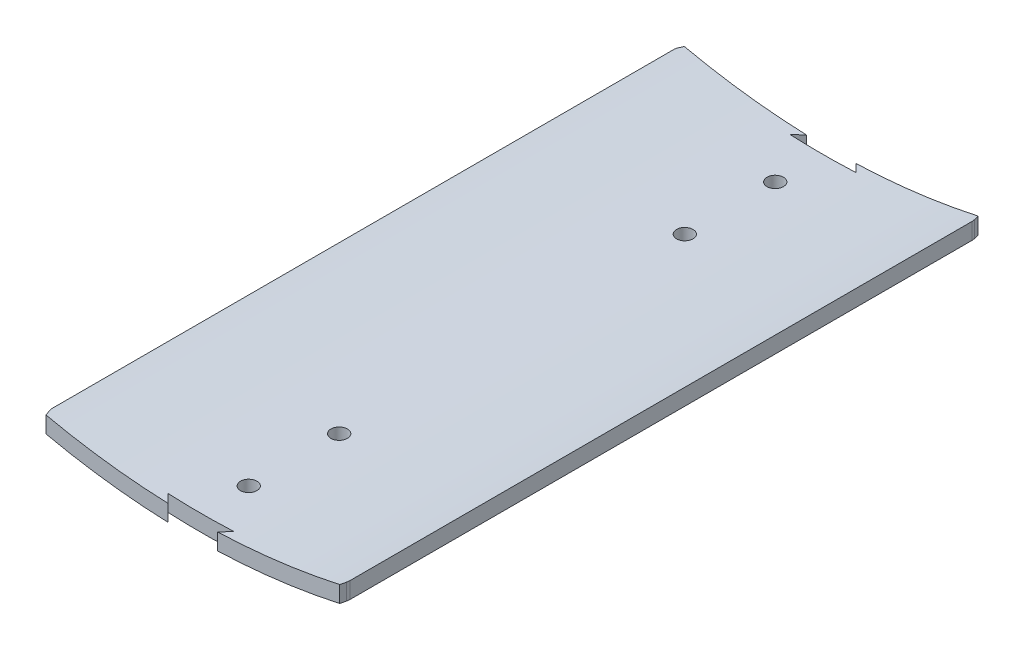
SolidWorks part; units mm, degrees
material "Maple"
ref_plane "Front Plane" through (0, 0, 0) normal (0, 0, 1) x (1, 0, 0)
ref_plane "Top Plane" through (0, 0, 0) normal (0, 1, 0) x (1, 0, 0)
ref_plane "Right Plane" through (0, 0, 0) normal (1, 0, 0) x (0, 0, -1)
sketch "Sketch1" plane through (0, 0, 0) normal (0, 0, 1) x (1, 0, 0)
  line L0 (0, 0) -> (230.1875, 0)
  line L1 (115.0937, 0) -> (115.0937, -12.7)
  line L2 (230.1875, 0) -> (230.1875, -12.7)
  line L3 (0, 0) -> (0, -12.7)
  arc A0 (230.1875, 0) -> (0, 0) centre (115.0938, 515.1686) cw
  arc A1 (230.1875, -12.7) -> (0, -12.7) centre (115.0938, 502.4686) cw
  point P6 (115.0937, -12.7)
  dimension "D1" = 2
extrude "Boss-Extrude1" add sketch "Sketch1" along normal blind 482.6 contours A1 L2 A0 L3 region at (115.0938, -14.8372, 0)
sketch "Sketch2" plane through (0, 0, 0) normal (0, 0, -1) x (-1, 0, 0)
  line L0 (-230.1875, 0) -> (-230.1875, -12.7)
  line L1 (0, 0) -> (0, -12.7)
  line L4 (-60.325, -19.05) -> (-60.325, -9.8511)
  line L5 (-169.8625, -19.05) -> (-169.8625, -9.8511)
  line L6 (-169.8625, -19.05) -> (-169.8625, -22.5511)
  line L7 (-60.325, -22.5511) -> (-60.325, -19.05)
  arc A0 (-230.1875, 0) -> (0, 0) centre (-115.0938, 515.1686) ccw
  arc A1 (-230.1875, -12.7) -> (0, -12.7) centre (-115.0938, 502.4686) ccw
  point P15 (-115.0938, -19.05)
  arc M1 (-230.1875, -12.7) -> (0, -12.7) centre (-115.0938, 502.4686) ccw
  line M2 (0, -12.7) -> (0, 0)
  arc M3 (0, 0) -> (-230.1875, 0) centre (-115.0938, 515.1686) cw
  line M4 (-230.1875, 0) -> (-230.1875, -12.7)
extrude "Boss-Extrude2" add sketch "Sketch2" along normal blind 98.425 contours L6 L5 M3 M4 M1 | L7 L4 M1 M2 M3 region at (200.025, -11.8738, 0) region at (30.1625, -11.8738, 0)
sketch "Sketch3" plane through (0, 0, 0) normal (0, 0, -1) x (-1, 0, 0)
  line L0 (-230.1875, -12.7) -> (-230.1875, 0)
  line L1 (0, 0) -> (0, -12.7)
  line L2 (-169.8625, -9.8511) -> (-169.8625, -22.5511)
  line L3 (-60.325, -9.8511) -> (-60.325, -22.5511)
  arc A0 (-230.1875, 0) -> (0, 0) centre (-115.0937, 515.1686) ccw
  arc A1 (-230.1875, -12.7) -> (0, -12.7) centre (-115.0938, 502.4686) ccw
  arc M1 (-169.8625, -22.5511) -> (-60.325, -22.5511) centre (-115.0938, 502.4686) ccw
  line M2 (-60.325, -22.5511) -> (-60.325, -9.8511)
  arc M3 (-60.325, -9.8511) -> (-169.8625, -9.8511) centre (-115.0938, 515.1686) cw
  line M4 (-169.8625, -9.8511) -> (-169.8625, -22.5511)
extrude "Boss-Extrude3" add sketch "Sketch3" along normal blind 254 contours M4 M1 M2 M3 region at (115.0938, -18.1014, 0)
sketch "Sketch4" plane through (0, 0, 482.6) normal (0, 0, 1) x (1, 0, 0)
  line L0 (0, 0) -> (0, -12.7)
  line L1 (230.1875, -12.7) -> (230.1875, 0)
  line L2 (60.325, -22.5511) -> (60.325, -9.8511)
  line L3 (169.8625, -22.5511) -> (169.8625, -9.8511)
  arc A0 (0, 0) -> (230.1875, 0) centre (115.0938, 515.1686) ccw
  arc A1 (0, -12.7) -> (230.1875, -12.7) centre (115.0938, 502.4686) ccw
  point P15 (115.0937, -19.05)
  arc M1 (0, -12.7) -> (230.1875, -12.7) centre (115.0938, 502.4686) ccw
  arc M3 (230.1875, 0) -> (0, 0) centre (115.0938, 515.1686) cw
extrude "Boss-Extrude4" add sketch "Sketch4" along normal blind 254 contours L3 L2 M1 M3 region at (115.0937, -18.1014, 482.6)
sketch "Sketch5" plane through (0, 0, 482.6) normal (0, 0, 1) x (1, 0, 0)
  line L0 (0, 0) -> (0, -12.7)
  line L1 (60.325, -9.8511) -> (60.325, -22.5511)
  line L2 (230.1875, 0) -> (230.1875, -12.7)
  line L3 (169.8625, -9.8511) -> (169.8625, -22.5511)
  arc A0 (0, 0) -> (230.1875, 0) centre (115.0938, 515.1686) ccw
  arc A1 (0, -12.7) -> (230.1875, -12.7) centre (115.0938, 502.4686) ccw
  arc M1 (0, -12.7) -> (60.325, -22.5511) centre (115.0938, 502.4686) ccw
  line M2 (60.325, -22.5511) -> (60.325, -9.8511)
  arc M3 (60.325, -9.8511) -> (0, 0) centre (115.0938, 515.1686) cw
  line M4 (0, 0) -> (0, -12.7)
extrude "Boss-Extrude5" add sketch "Sketch5" along normal blind 98.425 contours M4 M1 M2 M3 | L3 A1 L2 A0 region at (30.1625, -11.8738, 482.6) region at (200.025, -11.8738, 482.6)
ref_plane "Plane1" through (0, 0, 0) normal (0, -1, 0) x (-1, 0, 0)
sketch "Sketch6" plane through (0, 0, 0) normal (0, -1, 0) x (-1, 0, 0)
  line L0 (-115.0937, -736.6) -> (-115.0937, -482.6) construction
  line L1 (-169.8625, -736.6) -> (-60.325, -736.6) construction
  line L2 (-115.0938, 254) -> (-115.0937, 0) construction
  line L3 (-60.325, 254) -> (-169.8625, 254) construction
  line L4 (-230.1875, -482.6) -> (0, -482.6) construction
  line L5 (0, -581.025) -> (0, 98.425) construction
  line L6 (-230.1875, 0) -> (0, 0) construction
  line L7 (-60.325, -581.025) -> (0, -482.6) construction
  line L8 (-60.325, -736.6) -> (-60.325, -581.025) construction
  line L9 (-60.325, -682.625) -> (-169.8625, -682.625) construction
  line L10 (-169.8625, -736.6) -> (-169.8625, -581.025) construction
  line L11 (-169.8625, -581.025) -> (-230.1875, -482.6) construction
  line L12 (-60.325, 254) -> (-60.325, 98.425) construction
  line L13 (-60.325, 200.025) -> (-169.8625, 200.025) construction
  line L14 (-169.8625, 254) -> (-169.8625, 98.425) construction
  line L15 (-30.1625, -531.8125) -> (-200.025, -531.8125) construction
  line L16 (-230.1875, 0) -> (-169.8625, 98.425) construction
  line L17 (-60.325, 98.425) -> (0, 0) construction
  line L18 (-200.025, 49.2125) -> (-30.1625, 49.2125) construction
  line L19 (-30.1625, -531.8125) -> (-230.1875, -482.6) construction
  line L20 (-200.025, -531.8125) -> (0, -482.6) construction
  line L21 (0, 0) -> (-200.025, 49.2125) construction
  line L22 (-30.1625, 49.2125) -> (-230.1875, 0) construction
  line L23 (-230.1875, -510.9167) -> (0, -510.9167) construction
  line L24 (-230.1875, 28.3167) -> (0, 28.3167) construction
  line L25 (0, 0) -> (-8.6777, 28.3167) construction
  line L26 (-17.3554, -510.9167) -> (-8.6777, -510.9167) construction
  line L27 (-221.5098, 28.3167) -> (-230.1875, 0) construction
  line L28 (-8.6777, -510.9167) -> (0, -482.6) construction
  line L29 (-230.1875, -482.6) -> (-221.5098, -510.9167) construction
  line L30 (-212.8321, -510.9167) -> (-221.5098, -510.9167) construction
  line L31 (-8.6777, -510.9167) -> (0, -482.6) construction
  line L32 (-221.5098, -510.9167) -> (-230.1875, -482.6) construction
  line L33 (-17.3554, 28.3167) -> (-8.6777, 28.3167) construction
  line L34 (-8.6777, 28.3167) -> (0, 0) construction
  line L35 (-212.8321, 28.3167) -> (-221.5098, 28.3167) construction
  line L36 (-221.5098, 28.3167) -> (-230.1875, 0) construction
  line L38 (-60.325, -581.025) -> (0, -581.025)
  line L39 (0, -581.025) -> (0, -510.9167)
  line L40 (-60.325, -682.625) -> (-60.325, -736.6)
  line L41 (-60.325, -736.6) -> (-169.8625, -736.6)
  line L42 (-169.8625, -736.6) -> (-169.8625, -682.625)
  line L43 (-169.8625, -581.025) -> (-230.1875, -581.025)
  line L44 (-230.1875, -581.025) -> (-230.1875, -510.9167)
  line L45 (-230.1875, 0) -> (-230.1875, 98.425)
  line L46 (-230.1875, 98.425) -> (-169.8625, 98.425)
  line L47 (-169.8625, 200.025) -> (-169.8625, 254)
  line L48 (-169.8625, 254) -> (-60.325, 254)
  line L49 (-60.325, 254) -> (-60.325, 200.025)
  line L50 (-60.325, 98.425) -> (0, 98.425)
  line L51 (0, 98.425) -> (0, 0)
  line L52 (-230.1875, -482.6) -> (-230.1875, -510.9167)
  line L53 (0, -482.6) -> (0, -510.9167)
  arc A0 (-60.325, -682.625) -> (-169.8625, -682.625) centre (-115.0937, -682.625) cw
  arc A1 (-60.325, 200.025) -> (-169.8625, 200.025) centre (-115.0938, 200.025) ccw
  spline S0 degree 2 poles (-60.325, -581.025) (-55.0487, -517.0259) (-17.3554, -510.9167) knots 0 0 0 0.825721 0.825721 0.825721
  spline S1 degree 2 poles (-169.8625, -581.025) (-175.1388, -517.0259) (-212.8321, -510.9167) knots 0 0 0 0.825721 0.825721 0.825721
  spline S2 degree 2 poles (-169.8625, 98.425) (-175.1388, 34.4259) (-212.8321, 28.3167) knots 0 0 0 0.825721 0.825721 0.825721
  spline S3 degree 2 poles (-60.325, 98.425) (-55.0487, 34.4259) (-17.3554, 28.3167) knots 0 0 0 0.825721 0.825721 0.825721
  spline S4 degree 2 poles (-17.3554, -510.9167) (-8.6777, -510.9167) (0, -482.6) knots 0 0 0 1 1 1
  spline S5 degree 2 poles (-212.8321, -510.9167) (-221.5098, -510.9167) (-230.1875, -482.6) knots 0 0 0 1 1 1
  spline S6 degree 2 poles (-17.3554, 28.3167) (-8.6777, 28.3167) (0, 0) knots 0 0 0 1 1 1
  spline S7 degree 2 poles (-212.8321, 28.3167) (-221.5098, 28.3167) (-230.1875, 0) knots 0 0 0 1 1 1
  point P13 (-115.0937, -482.6)
  point P17 (-115.0937, 0)
  point P43 (-115.0938, -510.9167)
  point P44 (-17.3554, -510.9167)
  point P45 (-115.0938, 28.3167)
  point P49 (-115.0938, -510.9167)
  point P51 (-115.0938, 28.3167)
  point P53 (-212.8321, -510.9167)
  point P54 (-212.8321, 28.3167)
  point P55 (-17.3554, 28.3167)
extrude "Cut-Extrude1" cut sketch "Sketch6" along normal blind 98.425 contours L40 A0 L41 | L41 A0 L42 | S1 S5 L52 L44 L43 | S4 S0 L38 L39 L53 | S3 S6 L51 L50 | S7 S2 L46 L45 | A1 L48 L47 | A1 L49 L48 region at (25.0997, 0, 547.5668) region at (158.3996, 0, 724.4055) region at (71.7879, 0, 724.4055) region at (205.0878, 0, 547.5668) region at (205.0878, 0, -64.9668) region at (71.7879, 0, -241.8055) region at (158.3996, 0, -241.8055) region at (25.0997, 0, -64.9668)
sketch "Sketch8" plane through (0, 0, 0) normal (0, -1, 0) x (-1, 0, 0)
  line L0 (-60.325, 98.425) -> (-169.8625, 98.425) construction
  line L1 (0, 0) -> (-230.1875, 0) construction
  line L2 (-100.8698, 189.865) -> (-100.8698, 163.957)
  line L3 (-115.0938, 98.425) -> (-115.0937, 0)
  line L4 (0, -482.6) -> (-230.1875, -482.6)
  line L5 (0, -241.3) -> (-230.1875, -241.3)
  line L6 (0, -482.6) -> (0, 0) construction
  line L7 (-230.1875, -482.6) -> (-230.1875, 0) construction
  line L8 (-100.8698, 163.957) -> (-89.4398, 156.337)
  line L9 (-89.4398, 156.337) -> (-89.4398, 128.905)
  line L10 (-89.4398, 128.905) -> (-100.8698, 121.285)
  line L11 (-100.8698, 121.285) -> (-100.8698, 109.855)
  line L12 (-129.3177, 109.855) -> (-129.3177, 121.285)
  line L13 (-129.3177, 121.285) -> (-140.7477, 128.905)
  line L14 (-140.7477, 128.905) -> (-140.7477, 156.337)
  line L15 (-140.7477, 156.337) -> (-129.3177, 163.957)
  line L16 (-129.3177, 163.957) -> (-129.3177, 189.865)
  line L17 (-115.0938, 98.425) -> (-115.0938, 114.935) construction
  line L18 (-115.0938, 201.295) -> (-115.0938, 179.705) construction
  line L19 (-94.1388, 179.705) -> (-136.0488, 179.705) construction
  line L20 (-94.1388, 114.935) -> (-136.0488, 114.935) construction
  line L21 (-94.1387, -597.535) -> (-136.0487, -597.535) construction
  line L22 (-94.1387, -662.305) -> (-136.0487, -662.305) construction
  line L23 (-115.0937, -683.895) -> (-115.0937, -662.305) construction
  line L24 (-115.0937, -581.025) -> (-115.0937, -597.535) construction
  line L25 (-129.3177, -646.557) -> (-129.3177, -672.465)
  line L26 (-140.7477, -638.937) -> (-129.3177, -646.557)
  line L27 (-140.7477, -611.505) -> (-140.7477, -638.937)
  line L28 (-129.3177, -603.885) -> (-140.7477, -611.505)
  line L29 (-129.3177, -592.455) -> (-129.3177, -603.885)
  line L30 (-100.8698, -603.885) -> (-100.8698, -592.455)
  line L31 (-89.4398, -611.505) -> (-100.8698, -603.885)
  line L32 (-89.4398, -638.937) -> (-89.4398, -611.505)
  line L33 (-100.8698, -646.557) -> (-89.4398, -638.937)
  line L34 (-100.8698, -672.465) -> (-100.8698, -646.557)
  arc A0 (-100.8698, 189.865) -> (-129.3177, 189.865) centre (-115.0938, 186.7295) ccw
  arc A1 (-100.8698, 109.855) -> (-129.3177, 109.855) centre (-115.0938, 112.9905) cw
  circle A2 centre (-136.0488, 179.705) radius 2.54
  circle A3 centre (-136.0488, 114.935) radius 2.54
  circle A4 centre (-94.1388, 114.935) radius 2.54
  circle A5 centre (-94.1388, 179.705) radius 2.54
  circle A6 centre (-94.1387, -597.535) radius 2.54
  circle A7 centre (-136.0487, -597.535) radius 2.54
  circle A8 centre (-136.0487, -662.305) radius 2.54
  arc A9 (-100.8698, -592.455) -> (-129.3177, -592.455) centre (-115.0937, -595.5905) ccw
  arc A10 (-100.8698, -672.465) -> (-129.3177, -672.465) centre (-115.0937, -669.3295) cw
  circle A11 centre (-94.1387, -662.305) radius 2.54
  point P26 (-115.0937, 189.865)
  point P29 (-115.0938, 201.295)
  point P30 (-115.0938, 98.425)
  point P42 (-115.0938, 179.705)
  point P46 (-115.0938, 114.935)
  point P47 (-100.8698, 163.957)
  point P48 (-89.4398, 156.337)
  point P49 (-89.4398, 128.905)
  point P50 (-100.8698, 121.285)
  point P51 (-100.8698, 109.855)
  point P52 (-129.3177, 109.855)
  point P53 (-129.3177, 121.285)
  point P54 (-140.7477, 128.905)
  point P55 (-140.7477, 156.337)
  point P56 (-129.3177, 163.957)
  point P57 (-129.3177, 189.865)
  point P58 (-100.8698, 189.865)
  point P59 (-100.8698, 163.957)
  point P60 (-89.4398, 156.337)
  point P87 (-115.0937, -672.465)
extrude "Cut-Extrude2" cut sketch "Sketch8" along normal blind 30.48 contours A1 L11 L10 L9 L8 L2 A0 L16 L15 L14 L13 L12 | A4 | A10 L34 L33 L32 L31 L30 A9 L29 L28 L27 L26 L25 | A2 | A5 | A3 | A11 | A8 | A6 | A7 region at (115.0937, 0, -148.2319) region at (115.0937, 0, 630.8319) region at (94.1388, 0, -114.935)
fillet "Fillet2" radius 2.54 16 edges at (100.8698, -18.8583, -121.285) (89.4398, -18.4262, -128.905) (89.4398, -18.4262, -156.337) (100.8698, -18.8583, -163.957) (129.3177, -18.8583, -121.285) (140.7477, -18.4262, -128.905) (140.7477, -18.4262, -156.337) (129.3177, -18.8583, -163.957) (140.7477, -18.4262, 638.937) (140.7477, -18.4262, 611.505) (89.4398, -18.4262, 638.937) (89.4398, -18.4262, 611.505) (129.3177, -18.8583, 646.557) (129.3177, -18.8583, 603.885) (100.8698, -18.8583, 646.557) (100.8698, -18.8583, 603.885)
fillet "Fillet1" radius 7.62 4 edges at (0, -6.35, 0) (0, -6.35, 482.6) (230.1875, -6.35, 0) (230.1875, -6.35, 482.6)
sketch "Sketch9" plane through (0, 0, 0) normal (0, -1, 0) x (-1, 0, 0)
  line L0 (-115.0937, -736.6) -> (-115.0938, -88.7823) construction
  line L1 (-124.3844, -736.6) -> (-105.8031, -736.6) construction
  line L2 (-105.8031, 254) -> (-124.3844, 254) construction
  line L3 (0, -481.4477) -> (-230.1875, -481.4477) construction
  line L4 (-230.1875, -1.1523) -> (0, -1.1523) construction
  line L5 (-115.0937, -481.4477) -> (-115.0938, -470.0177) construction
  line L6 (-115.0938, -470.0177) -> (-115.0938, -400.1677) construction
  line L7 (0, -241.3) -> (-230.1875, -241.3) construction
  line L8 (0, -481.4477) -> (0, -1.1523) construction
  line L9 (-230.1875, -481.4477) -> (-230.1875, -1.1523) construction
  line L10 (-115.0938, -76.0823) -> (-115.0938, 254) construction
  circle A4 centre (-115.0938, -444.6177) radius 6.35
  circle A5 centre (-115.0938, -374.7677) radius 6.35
  circle A6 centre (-115.0938, -107.8323) radius 6.35
  circle A7 centre (-115.0938, -37.9823) radius 6.35
  point P23 (-115.0937, -82.4323)
  point P24 (-115.0937, -12.5823)
extrude "Cut-Extrude3" cut sketch "Sketch9" along normal blind 38.1
sketch "Sketch10" plane through (0, 0, 0) normal (0, -1, 0) x (-1, 0, 0)
  line L0 (0, -481.4477) -> (-230.1875, -481.4477) construction
  line L1 (-230.1875, -1.1523) -> (0, -1.1523) construction
  line L2 (0, -241.3) -> (-230.1875, -241.3) construction
  line L3 (0, -481.4477) -> (0, -1.1523) construction
  line L4 (-230.1875, -481.4477) -> (-230.1875, -1.1523) construction
  line L5 (-140.4937, -481.4477) -> (-89.6937, -481.4477)
  line L6 (-96.0437, -487.7977) -> (-1.6735, -487.7977)
  line L7 (-134.1437, -487.7977) -> (-228.514, -487.7977)
  line L10 (-134.1437, -487.7977) -> (-140.4937, -481.4477)
  line L11 (-96.0437, -487.7977) -> (-89.6937, -481.4477)
  line L12 (-134.1437, 5.1977) -> (-140.4937, -1.1523)
  line L13 (-134.1437, 5.1977) -> (-228.514, 5.1977)
  line L14 (-140.4937, -1.1523) -> (-89.6937, -1.1523)
  line L15 (-96.0438, 5.1977) -> (-89.6937, -1.1523)
  line L16 (-96.0438, 5.1977) -> (-1.6735, 5.1977)
  line L18 (-1.6735, -487.7977) -> (-228.514, -487.7977)
  line L19 (-1.6735, -487.7977) -> (-1.6735, -743.3709)
  line L20 (-1.6735, -743.3709) -> (-228.514, -743.3709)
  line L21 (-228.514, -487.7977) -> (-228.514, -743.3709)
  line L22 (-228.514, 5.1977) -> (-1.6735, 5.1977)
  line L23 (-228.514, 5.1977) -> (-228.514, 264.7545)
  line L24 (-228.514, 264.7545) -> (-1.6735, 264.7545)
  line L25 (-1.6735, 5.1977) -> (-1.6735, 264.7545)
  parabola Q0 (-0.3473, -483.7219) -> (-17.3554, -510.9167) focus (-17.3554, -508.2574) apex (-17.3554, -510.9167) construction
  parabola Q1 (-229.8402, -483.7219) -> (-212.8321, -510.9167) focus (-212.8321, -508.2574) apex (-212.8321, -510.9167) construction
  point P17 (-115.0937, -481.4477)
  point P20 (-89.6937, -481.4477)
  point P24 (-140.4937, -481.4477)
extrude "Cut-Extrude4" cut sketch "Sketch10" along normal blind 38.1 contours L7 L21 L20 L19 L6 L18 | L16 L25 L24 L23 L13 L22 | L18 L11 L5 L10 | L22 L12 L14 L15 region at (115.0938, 0, 484.4715) region at (115.0938, 0, 615.5843) region at (115.0938, 0, -1.8715) region at (115.0938, 0, -134.9761)
